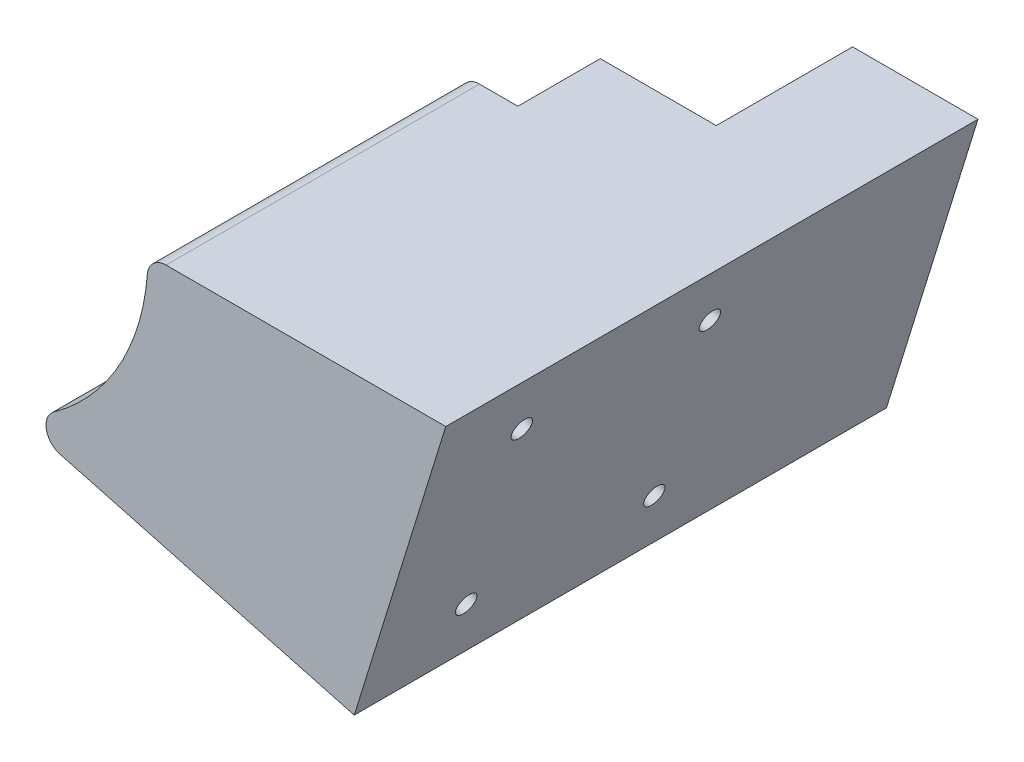
SolidWorks part; units mm, degrees
ref_plane "Front Plane" through (0, 0, 0) normal (0, 0, 1) x (1, 0, 0)
ref_plane "Top Plane" through (0, 0, 0) normal (0, 1, 0) x (1, 0, 0)
ref_plane "Right Plane" through (0, 0, 0) normal (1, 0, 0) x (0, 0, -1)
sketch "Sketch1" plane through (0, 0, 0) normal (0, 0, 1) x (1, 0, 0)
  line L0 (36, 0) -> (63.5, 0)
  line L1 (15, -61.7029) -> (15, -32.7261)
  arc A0 (36, 0) -> (15, -32.7261) centre (0, 0) cw
  arc A1 (63.5, 0) -> (15, -61.7029) centre (0, 0) cw
  dimension "D1" = 36
  dimension "D2" = 63.5
  dimension "D3" = 15
extrude "Boss-Extrude1" add sketch "Sketch1" along normal blind 50
sketch "Sketch2" plane through (0, 0, 0) normal (0, 0, -1) x (-1, 0, 0)
  line L0 (-63.5, 0) -> (-36, 0) construction
  line L1 (-15, -32.7261) -> (-15, -61.7029) construction
  line L4 (-45, 0) -> (-63.5, 0)
  line L5 (-15, -61.7029) -> (-15, -42.4264)
  arc A0 (-45, 0) -> (-15, -42.4264) centre (0, 0) ccw
  arc A2 (-63.5, 0) -> (-15, -61.7029) centre (0, 0) ccw
  dimension "D1" = 45
extrude "Boss-Extrude2" add sketch "Sketch2" along normal blind 13.15
sketch "Sketch3" plane through (0, 0, -13.15) normal (0, 0, -1) x (-1, 0, 0)
  line L0 (-63.5, 0) -> (-83.5, 0)
  line L1 (-15, -61.7029) -> (-15, -82.1416)
  arc A0 (-83.5, 0) -> (-15, -82.1416) centre (0, 0) ccw
  arc A1 (-36, 0) -> (-15, -32.7261) centre (0, 0) ccw construction
  arc A2 (-36, 0) -> (-15, -32.7261) centre (0, 0) ccw construction
  arc A3 (-63.5, 0) -> (-15, -61.7029) centre (0, 0) ccw construction
  arc A4 (-63.5, 0) -> (-15, -61.7029) centre (0, 0) ccw
  point P8 (-15.1743, -81.1426)
  dimension "D1" = 20
extrude "Boss-Extrude3" add sketch "Sketch3" along normal blind 21.75 and the other way up to surface (63.15 mm away) other way up to face at (36.2431, -26.4745, 50)
sketch "Sketch4" plane through (0, 0, 50) normal (0, 0, 1) x (1, 0, 0)
  line L0 (15, -32.7261) -> (68.901, -47.1689)
  line L1 (15, -32.7261) -> (15, -82.1416)
  line L2 (83.5, 0) -> (36, 0) construction
  arc A0 (15, -82.1416) -> (83.5, 0) centre (0, 0) ccw construction
  arc A1 (15, -82.1416) -> (68.901, -47.1689) centre (0, 0) ccw
  point P11 (68.901, -47.1689)
  dimension "D1" = 15
extrude "Cut-Extrude1" cut sketch "Sketch4" against normal through all
fillet "Fillet1" radius 3 2 edges at (36, 0, 25) (15, -32.7261, 25)
sketch "Sketch5" plane through (0, 0, 50) normal (0, 0, 1) x (1, 0, 0)
  line L0 (83.5, 0) -> (68.901, -47.1689)
  arc A0 (83.5, 0) -> (68.901, -47.1689) centre (0, 0) cw
  point P5 (0, 0)
extrude "Cut-Extrude2" cut sketch "Sketch5" against normal through all
hole_wizard "Tap Drill for M4x0.7 Tap1" positions "Sketch6" profile "Sketch8" hole size "M4x0.7" standard "ANSI Metric"
sketch "Sketch6" plane through (76.2005, -23.5844, 0) normal (0.9553, -0.2957, 0) x (0, 0, -1)
  point P0 (-35, 15)
  point P2 (-35, -15)
  point P4 (-5, 15)
  point P6 (-5, -15)
  point P10 (0, 0)
  point P11 (0, 0)
  point P12 (0, 0)
  point P13 (0, 0)
  point P14 (-35, -9.1859)
  dimension "D1" = 15
  dimension "D2" = 30
  dimension "D3" = 5
  dimension "D4" = 30
sketch "Sketch8" plane through (80.6355, -9.2551, 35) normal (0, 0, 1) x (0.2957, 0.9553, 0)
  line L0 (0, 0) -> (0, 10.9914)
  line L1 (0, 10.9914) -> (1.65, 10)
  line L2 (1.65, 10) -> (1.65, 0)
  line L5 (1.65, 0) -> (0, 0)
  line L10 (0, 10.9914) -> (-1.65, 10) construction
  line L11 (0, -6.35) -> (0, 107.95) construction
  dimension "Hole Dia." = 3.3
  dimension "Hole Depth" = 10
  dimension "Drill Angle" = 118
